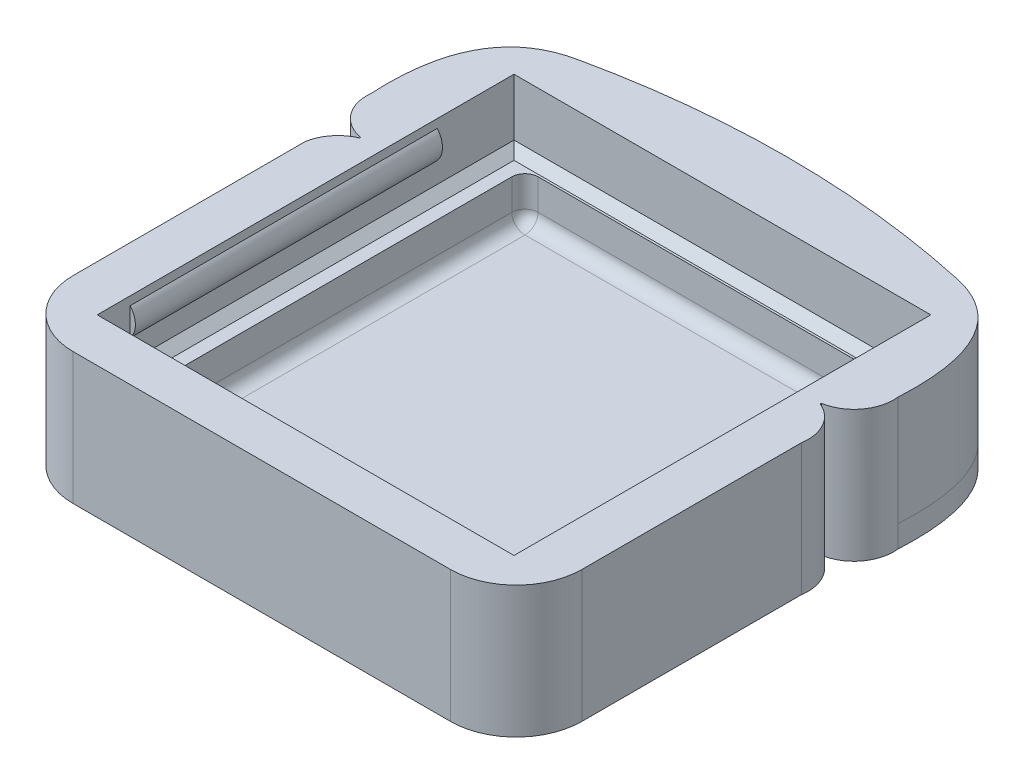
SolidWorks part; units mm, degrees
material "Teak"
ref_plane "Front Plane" through (0, 0, 0) normal (0, 0, 1) x (1, 0, 0)
ref_plane "Top Plane" through (0, 0, 0) normal (0, 1, 0) x (1, 0, 0)
ref_plane "Right Plane" through (0, 0, 0) normal (1, 0, 0) x (0, 0, -1)
sketch "Sketch2" plane through (0, 0, 0) normal (0, 1, 0) x (1, 0, 0)
  line L0 (-66.04, 22.225) -> (66.04, 22.225)
  line L1 (63.5, -66.675) -> (-63.5, -66.675)
  line L2 (63.5, -66.675) -> (63.5, 66.675)
  line L3 (63.5, 66.675) -> (-63.5, 66.675)
  line L4 (-63.5, -66.675) -> (-63.5, 66.675)
  line L5 (63.5, -66.675) -> (-63.5, 66.675) construction
  line L6 (63.5, 66.675) -> (-63.5, -66.675) construction
  line L7 (-73.66, 9.525) -> (-73.66, -53.975)
  line L8 (-54.61, -73.025) -> (54.61, -73.025)
  line L9 (73.66, -53.975) -> (73.66, 9.525)
  line L10 (-73.66, 9.525) -> (-73.66, 13.1711)
  arc A0 (-73.66, 9.525) -> (-66.04, 22.225) centre (-62.3051, 11.348) cw
  arc A1 (73.66, 9.525) -> (66.04, 22.225) centre (62.3051, 11.348) ccw
  arc A2 (-66.04, 22.225) -> (-76.2, 34.925) centre (-64.77, 33.655) cw
  arc A3 (66.04, 22.225) -> (76.2, 34.925) centre (64.77, 33.655) ccw
  arc A4 (-54.2615, 73.3341) -> (54.2615, 73.3341) centre (0, -178.2209) cw
  arc A5 (73.66, -53.975) -> (54.61, -73.025) centre (54.61, -53.975) cw
  arc A6 (-73.66, -53.975) -> (-54.61, -73.025) centre (-54.61, -53.975) ccw
  spline S0 degree 2 poles (-54.2615, 73.3341) (-78.0337, 68.7721) (-76.2, 34.925) knots 0 0 0 1 1 1
  spline S1 degree 2 poles (54.2615, 73.3341) (78.0337, 68.7721) (76.2, 34.925) knots 0 0 0 1 1 1
  point P0 (0, 0)
  dimension "D11" = 11.5003
  dimension "D12" = 11.5003
  dimension "D14" = 11.5003
  dimension "D15" = 11.5003
  dimension "D17" = 19.05
  dimension "D1" = 133.35
  dimension "D2" = 127
  dimension "D3" = 44.45
  dimension "D4" = 2.54
  dimension "D5" = 2.54
  dimension "D6" = 10.16
  dimension "D7" = 10.16
  dimension "D8" = 6.35
  dimension "D9" = 12.7
  dimension "D10" = 12.7
  dimension "D13" = 12.7
extrude "Boss-Extrude1" add sketch "Sketch2" along normal blind 6.35 contours L7 A6 L8 A5 L9 A1 L0 L2 L1 L4 A0 L10 | L4 L1 L2 L0 | L4 L0 L2 | A2 L0 L4 L10 | S1 A4 S0 L10 L4 L3 L2 | L4 L2 L3 | L0 A3 L2 region at (-72.4781, 0, -27.4885) region at (-64.77, 0, -20.4695) region at (0, 0, -44.45) region at (0, 0, 22.225)
sketch "Sketch3" plane through (0, 6.35, 0) normal (0, 1, 0) x (1, 0, 0)
  line L1 (-53.975, 57.15) -> (53.975, 57.15)
  line L2 (-53.975, 57.15) -> (-53.975, -57.15)
  line L3 (-53.975, -57.15) -> (53.975, -57.15)
  line L4 (53.975, 57.15) -> (53.975, -57.15)
  line L5 (-53.975, 57.15) -> (53.975, -57.15) construction
  line L6 (-53.975, -57.15) -> (53.975, 57.15) construction
  line L8 (-66.675, 63.5) -> (66.675, 63.5)
  line L9 (-66.675, 63.5) -> (-66.675, -63.5)
  line L10 (-66.675, -63.5) -> (66.675, -63.5)
  line L11 (66.675, 63.5) -> (66.675, -63.5)
  line L12 (-66.675, 63.5) -> (66.675, -63.5) construction
  line L13 (-66.675, -63.5) -> (66.675, 63.5) construction
  point P0 (0, 0)
  point P10 (0, 0)
  dimension "D1" = 107.95
  dimension "D2" = 114.3
  dimension "D3" = 12.7
  dimension "D4" = 6.35
extrude "Boss-Extrude2" add sketch "Sketch3" along normal blind 12.7
sketch "Sketch4" plane through (0, 19.05, 0) normal (0, 1, 0) x (1, 0, 0)
  line L0 (53.975, -57.15) -> (53.975, 57.15) construction
  line L1 (-66.675, 63.5) -> (66.675, 63.5)
  line L2 (-66.675, 63.5) -> (-66.675, -63.5)
  line L3 (-66.675, -63.5) -> (66.675, -63.5)
  line L4 (66.675, 63.5) -> (66.675, -63.5)
  line L5 (-66.675, 63.5) -> (66.675, -63.5) construction
  line L6 (-66.675, -63.5) -> (66.675, 63.5) construction
  line L7 (-60.325, 60.325) -> (60.325, 60.325)
  line L8 (-60.325, 60.325) -> (-60.325, -60.325)
  line L9 (-60.325, -60.325) -> (60.325, -60.325)
  line L10 (60.325, 60.325) -> (60.325, -60.325)
  line L11 (-60.325, 60.325) -> (60.325, -60.325) construction
  line L12 (-60.325, -60.325) -> (60.325, 60.325) construction
  point P0 (0, 0)
  point P7 (0, 0)
  dimension "D1" = 6.35
  dimension "D2" = 3.175
extrude "Boss-Extrude3" add sketch "Sketch4" along normal blind 19.05
fillet "Fillet1" radius 6.35 4 edges at (-66.675, 22.225, -63.5) (66.675, 22.225, -63.5) (66.675, 22.225, 63.5) (-66.675, 22.225, 63.5)
fillet "Fillet2" radius 3.81 4 edges at (-53.975, 6.35, 0) (0, 6.35, 57.15) (53.975, 6.35, 0) (0, 6.35, -57.15)
sketch "Sketch5" plane through (0, 0, 0) normal (0, 0, 1) x (1, 0, 0)
  line L4 (60.325, 35.6221) -> (60.325, 27.5579)
  line L5 (-60.325, 35.6221) -> (-60.325, 27.5579)
  arc A0 (60.325, 35.6221) -> (60.325, 27.5579) centre (64.897, 31.59) ccw
  arc A1 (-60.325, 35.6221) -> (-60.325, 27.5579) centre (-64.897, 31.59) cw
  dimension "D3" = 12.192
  dimension "D5" = 4.572
extrude "Boss-Extrude4" add sketch "Sketch5" along normal blind 50.8 and the other way blind 38.1
chamfer "Chamfer1" distance 2.54 angle 45 4 edges at (0, 19.05, 60.325) (60.325, 19.05, 0) (0, 19.05, -60.325) (-60.325, 19.05, 0)
sketch "Sketch6" plane through (0, 0, 0) normal (0, -1, 0) x (1, 0, 0)
  text T0 "<b>SJKELLY</b>"
extrude "Cut-Extrude1" cut sketch "Sketch6" against normal blind 2.54
fillet "Fillet3" radius 3.81 8 edges at (-52.8591, 7.4659, -56.0341) (-52.8591, 7.4659, 56.0341) (52.8591, 7.4659, 56.0341) (52.8591, 7.4659, -56.0341) (-53.975, 14.605, -57.15) (-53.975, 14.605, 57.15) (53.975, 14.605, 57.15) (53.975, 14.605, -57.15)
sketch "Sketch7" plane through (0, 6.35, 0) normal (0, 1, 0) x (1, 0, 0)
  line L0 (66.675, 21.9858) -> (66.675, -57.15) construction
  line L1 (60.325, -63.5) -> (-60.325, -63.5) construction
  line L2 (-66.675, -57.15) -> (-66.675, 21.9858) construction
  line L3 (-73.66, 13.1711) -> (-73.66, -53.975) construction
  line L4 (-54.61, -73.025) -> (54.61, -73.025) construction
  line L5 (73.66, -53.975) -> (73.66, 9.525) construction
  line L6 (66.675, 57.15) -> (66.675, 22.3135) construction
  line L7 (-66.675, 22.3135) -> (-66.675, 57.15) construction
  line L8 (-60.325, 63.5) -> (60.325, 63.5) construction
  line L9 (66.675, 21.9858) -> (66.675, -57.15)
  line L10 (60.325, -63.5) -> (-60.325, -63.5)
  line L11 (-66.675, -57.15) -> (-66.675, 21.9858)
  line L12 (-73.66, 13.1711) -> (-73.66, -53.975)
  line L13 (-54.61, -73.025) -> (54.61, -73.025)
  line L14 (73.66, -53.975) -> (73.66, 9.525)
  line L15 (66.675, 57.15) -> (66.675, 22.3135)
  line L16 (-66.675, 22.3135) -> (-66.675, 57.15)
  line L17 (-60.325, 63.5) -> (60.325, 63.5)
  arc A0 (60.325, -63.5) -> (66.675, -57.15) centre (60.325, -57.15) ccw construction
  arc A1 (-66.675, -57.15) -> (-60.325, -63.5) centre (-60.325, -57.15) ccw construction
  arc A2 (-66.675, 21.9858) -> (-73.66, 13.1711) centre (-62.3051, 11.348) ccw construction
  arc A3 (-73.66, -53.975) -> (-54.61, -73.025) centre (-54.61, -53.975) ccw construction
  arc A4 (54.61, -73.025) -> (73.66, -53.975) centre (54.61, -53.975) ccw construction
  arc A5 (73.66, 9.525) -> (66.675, 21.9858) centre (62.3051, 11.348) ccw construction
  arc A6 (66.675, 22.3135) -> (76.2, 34.925) centre (64.77, 33.655) ccw construction
  arc A7 (54.2615, 73.3341) -> (-54.2615, 73.3341) centre (0, -178.2209) ccw construction
  arc A8 (-76.2, 34.925) -> (-66.675, 22.3135) centre (-64.77, 33.655) ccw construction
  arc A9 (-60.325, 63.5) -> (-66.675, 57.15) centre (-60.325, 57.15) ccw construction
  arc A10 (66.675, 57.15) -> (60.325, 63.5) centre (60.325, 57.15) ccw construction
  arc A11 (60.325, -63.5) -> (66.675, -57.15) centre (60.325, -57.15) ccw
  arc A12 (-66.675, -57.15) -> (-60.325, -63.5) centre (-60.325, -57.15) ccw
  arc A13 (-66.675, 21.9858) -> (-73.66, 13.1711) centre (-62.3051, 11.348) ccw
  arc A14 (-73.66, -53.975) -> (-54.61, -73.025) centre (-54.61, -53.975) ccw
  arc A15 (54.61, -73.025) -> (73.66, -53.975) centre (54.61, -53.975) ccw
  arc A16 (73.66, 9.525) -> (66.675, 21.9858) centre (62.3051, 11.348) ccw
  arc A17 (66.675, 22.3135) -> (76.2, 34.925) centre (64.77, 33.655) ccw
  arc A18 (54.2615, 73.3341) -> (-54.2615, 73.3341) centre (0, -178.2209) ccw
  arc A19 (-76.2, 34.925) -> (-66.675, 22.3135) centre (-64.77, 33.655) ccw
  arc A20 (-60.325, 63.5) -> (-66.675, 57.15) centre (-60.325, 57.15) ccw
  arc A21 (66.675, 57.15) -> (60.325, 63.5) centre (60.325, 57.15) ccw
  parabola Q0 (76.2, 34.925) -> (54.2615, 73.3341) focus (59.2742, 59.1306) apex (66.6645, 67.5829) construction
  parabola Q1 (-54.2615, 73.3341) -> (-76.2, 34.925) focus (-59.2742, 59.1306) apex (-66.6645, 67.5829) construction
  parabola Q2 (76.2, 34.925) -> (54.2615, 73.3341) focus (59.2742, 59.1306) apex (66.6645, 67.5829)
  parabola Q3 (-54.2615, 73.3341) -> (-76.2, 34.925) focus (-59.2742, 59.1306) apex (-66.6645, 67.5829)
extrude "Boss-Extrude5" add sketch "Sketch7" along normal blind 31.75
